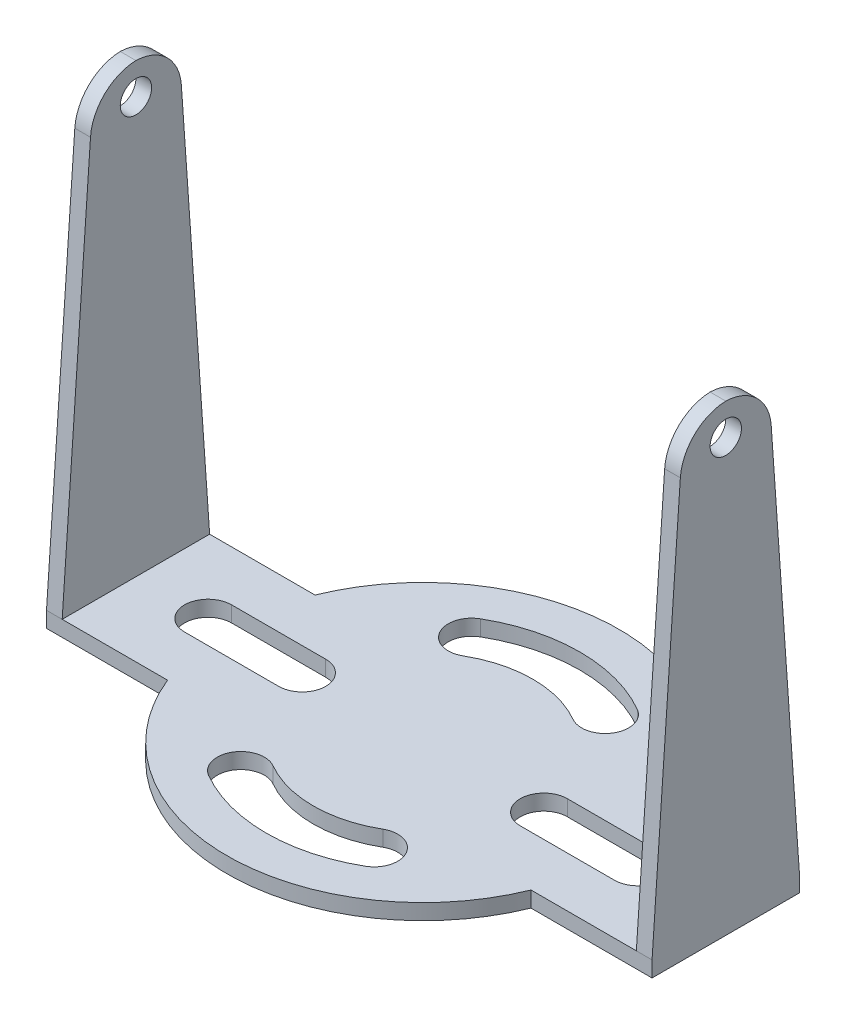
SolidWorks part; units mm, degrees
ref_plane "前视基准面" through (0, 0, 0) normal (0, 0, 1) x (1, 0, 0)
ref_plane "上视基准面" through (0, 0, 0) normal (0, 1, 0) x (1, 0, 0)
ref_plane "右视基准面" through (0, 0, 0) normal (1, 0, 0) x (0, 0, -1)
sketch "草图2" plane through (0, 0, 0) normal (0, 1, 0) x (1, 0, 0)
  line L1 (19.3, -4.7) -> (-19.3, -4.7)
  line L2 (19.3, -4.7) -> (19.3, 4.7)
  line L3 (19.3, 4.7) -> (-19.3, 4.7)
  line L4 (-19.3, -4.7) -> (-19.3, 4.7)
  line L5 (19.3, -4.7) -> (-19.3, 4.7) construction
  line L6 (19.3, 4.7) -> (-19.3, -4.7) construction
  point P0 (0, 0)
  dimension "D1" = 38.6
  dimension "D2" = 9.4
extrude "凸台-拉伸1" add sketch "草图2" along normal blind 1
sketch "草图3" plane through (0, 1, 0) normal (0, 1, 0) x (1, 0, 0)
  line L0 (-19.3, -4.7) -> (19.3, -4.7) construction
  line L1 (-19.3, 4.7) -> (-18.3, 4.7)
  line L2 (-19.3, 4.7) -> (-19.3, -4.7)
  line L3 (-19.3, -4.7) -> (-18.3, -4.7)
  line L4 (-18.3, 4.7) -> (-18.3, -4.7)
  line L5 (0, 0) -> (0, 4.7) construction
  line L6 (19.3, 4.7) -> (18.3, 4.7)
  line L7 (19.3, 4.7) -> (19.3, -4.7)
  line L8 (19.3, -4.7) -> (18.3, -4.7)
  line L9 (18.3, 4.7) -> (18.3, -4.7)
  line L10 (19.3, 4.7) -> (-19.3, 4.7) construction
  dimension "D1" = 1
extrude "凸台-拉伸2" add sketch "草图3" along normal blind 28.5
sketch "草图4" plane through (0, 1, 0) normal (0, 1, 0) x (1, 0, 0)
  line L0 (0, 0) -> (7, 0) construction
  line L4 (0, 0) -> (4.25, 7.3612)
  line L5 (0, 8.5) -> (0, 0) construction
  circle A0 centre (0, 0) radius 12.5
  circle A1 centre (0, 0) radius 7 construction
  arc A2 (-4.25, -7.3612) -> (4.25, -7.3612) centre (0, 0) ccw construction
  arc A3 (5, -8.6603) -> (-5, -8.6603) centre (0, 0) cw
  arc A4 (-4.25, 7.3612) -> (4.25, 7.3612) centre (0, 0) cw construction
  arc A5 (5, 8.6603) -> (-5, 8.6603) centre (0, 0) ccw
  arc A6 (3.5, 6.0622) -> (-3.5, 6.0622) centre (0, 0) ccw
  arc A7 (3.5, 6.0622) -> (5, 8.6603) centre (4.25, 7.3612) ccw
  arc A8 (-5, 8.6603) -> (-3.5, 6.0622) centre (-4.25, 7.3612) ccw
  arc A9 (3.5, -6.0622) -> (-3.5, -6.0622) centre (0, 0) cw
  arc A10 (3.5, -6.0622) -> (5, -8.6603) centre (4.25, -7.3612) cw
  arc A11 (-5, -8.6603) -> (-3.5, -6.0622) centre (-4.25, -7.3612) cw
  point P7 (0, -8.5)
  point P16 (0, 8.5)
  dimension "D1" = 25
  dimension "D2" = 14
  dimension "D6" = 3
  dimension "D7" = 30
extrude "凸台-拉伸3" add sketch "草图4" against normal blind 1
sketch "草图5" plane through (0, 1, 0) normal (0, 1, 0) x (1, 0, 0)
  line L0 (13.7, 0) -> (7.7, 0) construction
  line L1 (13.7, -1.5) -> (7.7, -1.5)
  line L2 (13.7, 1.5) -> (7.7, 1.5)
  line L3 (0, 0) -> (0, -7) construction
  line L4 (-13.7, 0) -> (-7.7, 0) construction
  line L5 (-13.7, -1.5) -> (-7.7, -1.5)
  line L6 (-13.7, 1.5) -> (-7.7, 1.5)
  line L7 (19.3, -4.7) -> (19.3, 4.7) construction
  arc A0 (13.7, -1.5) -> (13.7, 1.5) centre (13.7, 0) ccw
  arc A1 (7.7, 1.5) -> (7.7, -1.5) centre (7.7, 0) ccw
  arc A2 (-3.5, -6.0622) -> (3.5, -6.0622) centre (0, 0) ccw construction
  arc A3 (-13.7, -1.5) -> (-13.7, 1.5) centre (-13.7, 0) cw
  arc A4 (-7.7, 1.5) -> (-7.7, -1.5) centre (-7.7, 0) cw
  point P3 (10.7, 0)
  point P15 (-10.7, 0)
  dimension "D1" = 3
  dimension "D2" = 5.6
  dimension "D3" = 6
extrude "切除-拉伸1" cut sketch "草图5" against normal through all
sketch "草图6" plane through (19.3, 0, 0) normal (1, 0, 0) x (0, 0, -1)
  line L0 (-4.7, 1) -> (-2.7, 29.5)
  line L1 (-4.7, 29.5) -> (4.7, 29.5) construction
  line L2 (-2.7, 29.5) -> (-4.7, 29.5)
  line L3 (-4.7, 29.5) -> (-4.7, 1)
  line L4 (-4.7, 1) -> (-4.5743, 0.6631)
  line L5 (0, 0) -> (0, 29.5) construction
  line L6 (4.7, 1) -> (4.5743, 0.6631)
  line L7 (4.7, 29.5) -> (4.7, 1)
  line L8 (2.7, 29.5) -> (4.7, 29.5)
  line L9 (4.7, 1) -> (2.7, 29.5)
  line M4 (4.7, 29.5) -> (-4.7, 29.5)
  line M5 (-4.7, 29.5) -> (-4.7, 0)
  dimension "D1" = 2
extrude "切除-拉伸2" cut sketch "草图6" against normal through all contours L0 M5 M4 | L9 L8 L7
sketch "草图7" plane through (19.3, 0, 0) normal (1, 0, 0) x (0, 0, -1)
  line L0 (-2.7, 29.5) -> (2.7, 29.5) construction
  circle A0 centre (0, 27.5) radius 1
  point P5 (0, 29.5)
  dimension "D1" = 2
  dimension "D2" = 2
extrude "切除-拉伸3" cut sketch "草图7" against normal through all
fillet "圆角1" radius 3 4 edges at (-18.8, 29.5, -2.7) (-18.8, 29.5, 2.7) (18.8, 29.5, -2.7) (18.8, 29.5, 2.7)
